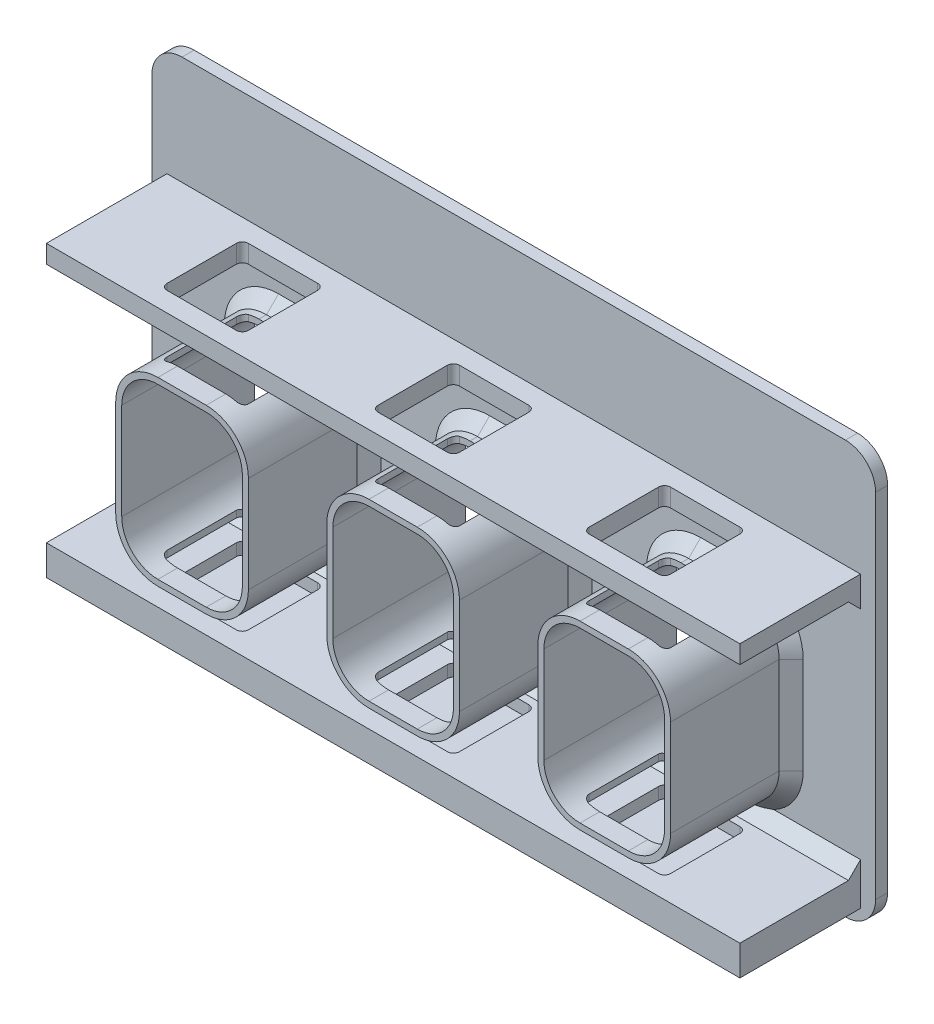
SolidWorks part; units mm, degrees
ref_plane "Front Plane" through (0, 0, 0) normal (0, 0, 1) x (1, 0, 0)
ref_plane "Top Plane" through (0, 0, 0) normal (0, 1, 0) x (1, 0, 0)
ref_plane "Right Plane" through (0, 0, 0) normal (1, 0, 0) x (0, 0, -1)
sketch "Sketch1" plane through (0, 0, 0) normal (0, 0, 1) x (1, 0, 0)
  line L1 (-60, 37.5) -> (60, 37.5)
  line L2 (-60, 37.5) -> (-60, -37.5)
  line L3 (-60, -37.5) -> (60, -37.5)
  line L4 (60, 37.5) -> (60, -37.5)
  line L5 (-60, 37.5) -> (60, -37.5) construction
  line L6 (-60, -37.5) -> (60, 37.5) construction
  point P0 (0, 0)
  dimension "D1" = 75
  dimension "D2" = 120
extrude "Boss-Extrude1" add sketch "Sketch1" along normal blind 2
sketch "Sketch2" plane through (0, 0, 2) normal (0, 0, 1) x (1, 0, 0)
  line L0 (-60, 37.5) -> (-60, -37.5) construction
  line L1 (-57.5, -35) -> (57.5, -35)
  line L2 (-57.5, -35) -> (-57.5, -30)
  line L3 (-57.5, -30) -> (57.5, -30)
  line L4 (57.5, -35) -> (57.5, -30)
  line L5 (-57.5, 13) -> (57.5, 13)
  line L6 (-57.5, 13) -> (-57.5, 10)
  line L7 (-57.5, 10) -> (57.5, 10)
  line L8 (57.5, 13) -> (57.5, 10)
  line L9 (60, -37.5) -> (60, 37.5) construction
  line L10 (-60, -37.5) -> (60, -37.5) construction
  dimension "D1" = 5
  dimension "D2" = 2.5
  dimension "D3" = 2.5
  dimension "D4" = 2.5
  dimension "D5" = 40
  dimension "D6" = 3
  dimension "D7" = 2.5
  dimension "D8" = 2.5
extrude "Boss-Extrude2" add sketch "Sketch2" along normal blind 20
sketch "Sketch3" plane through (0, 0, 2) normal (0, 0, 1) x (1, 0, 0)
  line L0 (-60, 37.5) -> (-60, -37.5) construction
  line L1 (-45, 2) -> (-25, 2)
  line L2 (-45, 2) -> (-45, -26)
  line L3 (-45, -26) -> (-25, -26)
  line L4 (-25, 2) -> (-25, -26)
  line L5 (-10, 2) -> (10, 2)
  line L6 (-10, 2) -> (-10, -26)
  line L7 (-10, -26) -> (10, -26)
  line L8 (10, 2) -> (10, -26)
  line L9 (25, 2) -> (45, 2)
  line L10 (25, 2) -> (25, -26)
  line L11 (25, -26) -> (45, -26)
  line L12 (45, 2) -> (45, -26)
  line L13 (-57.5, 10) -> (57.5, 10) construction
  line L14 (57.5, -30) -> (-57.5, -30) construction
  dimension "D1" = 20
  dimension "D2" = 20
  dimension "D3" = 20
  dimension "D4" = 15
  dimension "D5" = 15
  dimension "D6" = 15
  dimension "D7" = 8
  dimension "D8" = 4
  dimension "D9" = 4
  dimension "D10" = 4
extrude "Cut-Extrude1" cut sketch "Sketch3" against normal blind 20
sketch "Sketch4" plane through (0, 0, 2) normal (0, 0, 1) x (1, 0, 0)
  line L1 (-45, 2) -> (-25, 2)
  line L2 (-45, 2) -> (-45, -26)
  line L3 (-45, -26) -> (-25, -26)
  line L4 (-25, 2) -> (-25, -26)
  line L5 (-46, 3) -> (-24, 3)
  line L6 (-46, 3) -> (-46, -27)
  line L7 (-46, -27) -> (-24, -27)
  line L8 (-24, 3) -> (-24, -27)
  line L9 (-10, 2) -> (10, 2)
  line L10 (-10, 2) -> (-10, -26)
  line L11 (-10, -26) -> (10, -26)
  line L12 (10, 2) -> (10, -26)
  line L13 (-11, 3) -> (11, 3)
  line L14 (-11, 3) -> (-11, -27)
  line L15 (-11, -27) -> (11, -27)
  line L16 (11, 3) -> (11, -27)
  line L17 (25, 2) -> (45, 2)
  line L18 (25, 2) -> (25, -26)
  line L19 (25, -26) -> (45, -26)
  line L20 (45, 2) -> (45, -26)
  line L21 (24, 3) -> (46, 3)
  line L22 (24, 3) -> (24, -27)
  line L23 (24, -27) -> (46, -27)
  line L24 (46, 3) -> (46, -27)
  dimension "D1" = 1
  dimension "D2" = 1
  dimension "D3" = 1
  dimension "D4" = 1
  dimension "D5" = 1
  dimension "D6" = 1
  dimension "D7" = 1
  dimension "D8" = 1
  dimension "D9" = 1
  dimension "D10" = 1
  dimension "D11" = 1
  dimension "D12" = 1
extrude "Boss-Extrude3" add sketch "Sketch4" along normal blind 20
fillet "Fillet1" radius 6 12 edges at (45, 2, 11) (25, 2, 11) (45, -26, 11) (25, -26, 11) (10, 2, 11) (-10, 2, 11) (10, -26, 11) (-10, -26, 11) (-45, -26, 11) (-25, -26, 11) (-45, 2, 11) (-25, 2, 11)
fillet "Fillet2" radius 7 12 edges at (46, -27, 12) (46, 3, 12) (24, -27, 12) (24, 3, 12) (11, -27, 12) (11, 3, 12) (-11, 3, 12) (-11, -27, 12) (-46, -27, 12) (-24, -27, 12) (-24, 3, 12) (-46, 3, 12)
sketch "Sketch5" plane through (0, 13, 0) normal (0, 1, 0) x (1, 0, 0)
  line L1 (40.75, -18.75) -> (29.25, -18.75)
  line L2 (41.75, -17.75) -> (41.75, -6.25)
  line L3 (40.75, -5.25) -> (29.25, -5.25)
  line L4 (28.25, -17.75) -> (28.25, -6.25)
  line L5 (41.75, -18.75) -> (28.25, -5.25) construction
  line L6 (41.75, -5.25) -> (28.25, -18.75) construction
  line L7 (5.75, -18.75) -> (-5.75, -18.75)
  line L8 (6.75, -17.75) -> (6.75, -6.25)
  line L9 (5.75, -5.25) -> (-5.75, -5.25)
  line L10 (-6.75, -17.75) -> (-6.75, -6.25)
  line L11 (6.75, -18.75) -> (-6.75, -5.25) construction
  line L12 (6.75, -5.25) -> (-6.75, -18.75) construction
  line L13 (-29.25, -18.75) -> (-40.75, -18.75)
  line L14 (-28.25, -17.75) -> (-28.25, -6.25)
  line L15 (-29.25, -5.25) -> (-40.75, -5.25)
  line L16 (-41.75, -17.75) -> (-41.75, -6.25)
  line L17 (-28.25, -18.75) -> (-41.75, -5.25) construction
  line L18 (-28.25, -5.25) -> (-41.75, -18.75) construction
  line L19 (57.5, -2) -> (-57.5, -2) construction
  line L22 (57.5, -22) -> (57.5, -2) construction
  arc A0 (-40.75, -5.25) -> (-41.75, -6.25) centre (-40.75, -6.25) ccw
  arc A1 (-28.25, -6.25) -> (-29.25, -5.25) centre (-29.25, -6.25) ccw
  arc A2 (-40.75, -18.75) -> (-41.75, -17.75) centre (-40.75, -17.75) cw
  arc A3 (-29.25, -18.75) -> (-28.25, -17.75) centre (-29.25, -17.75) ccw
  arc A4 (-5.75, -5.25) -> (-6.75, -6.25) centre (-5.75, -6.25) ccw
  arc A5 (6.75, -6.25) -> (5.75, -5.25) centre (5.75, -6.25) ccw
  arc A6 (-5.75, -18.75) -> (-6.75, -17.75) centre (-5.75, -17.75) cw
  arc A7 (5.75, -18.75) -> (6.75, -17.75) centre (5.75, -17.75) ccw
  arc A8 (29.25, -5.25) -> (28.25, -6.25) centre (29.25, -6.25) ccw
  arc A9 (41.75, -6.25) -> (40.75, -5.25) centre (40.75, -6.25) ccw
  arc A10 (29.25, -18.75) -> (28.25, -17.75) centre (29.25, -17.75) cw
  arc A11 (40.75, -18.75) -> (41.75, -17.75) centre (40.75, -17.75) ccw
  point P0 (35, -12)
  point P5 (0, -12)
  point P10 (-35, -12)
  dimension "D13" = 1
  dimension "D1" = 13.5
  dimension "D2" = 13.5
  dimension "D3" = 3.25
  dimension "D4" = 13.5
  dimension "D5" = 13.5
  dimension "D6" = 3.25
  dimension "D7" = 13.5
  dimension "D8" = 13.5
  dimension "D9" = 3.25
  dimension "D10" = 21.5
  dimension "D11" = 21.5
  dimension "D12" = 15.75
extrude "Cut-Extrude2" cut sketch "Sketch5" against normal blind 45
sketch "Sketch6" plane through (0, 0, 2) normal (0, 0, 1) x (1, 0, 0)
  line L0 (60, -37.5) -> (60, 37.5) construction
  line L1 (-60, 37.5) -> (60, 37.5)
  line L2 (-60, 37.5) -> (-60, 31)
  line L3 (-60, 31) -> (60, 31)
  line L4 (60, 37.5) -> (60, 31)
  line L5 (57.5, 13) -> (-57.5, 13) construction
  dimension "D1" = 18
extrude "Cut-Extrude3" cut sketch "Sketch6" against normal blind 45
fillet "Fillet3" radius 5 4 edges at (-60, -37.5, 1) (60, -37.5, 1) (60, 31, 1) (-60, 31, 1)
chamfer "Chamfer1" distance 2 angle 45 1 edges at (0, 10, 2)
chamfer "Chamfer2" distance 2 angle 45 24 edges at (-46, -12, 2) (-43.9497, -24.9497, 2) (-43.9497, 0.9497, 2) (-35, -27, 2) (-35, 3, 2) (-26.0503, -24.9497, 2) (-26.0503, 0.9497, 2) (-24, -12, 2) (-11, -12, 2) (-8.9497, -24.9497, 2) (-8.9497, 0.9497, 2) (0, -27, 2) (0, 3, 2) (8.9497, -24.9497, 2) (8.9497, 0.9497, 2) (11, -12, 2) (24, -12, 2) (26.0503, -24.9497, 2) (26.0503, 0.9497, 2) (35, -27, 2) (35, 3, 2) (43.9497, -24.9497, 2) (43.9497, 0.9497, 2) (46, -12, 2)
chamfer "Chamfer3" distance 2 angle 45 1 edges at (0, -30, 2)
